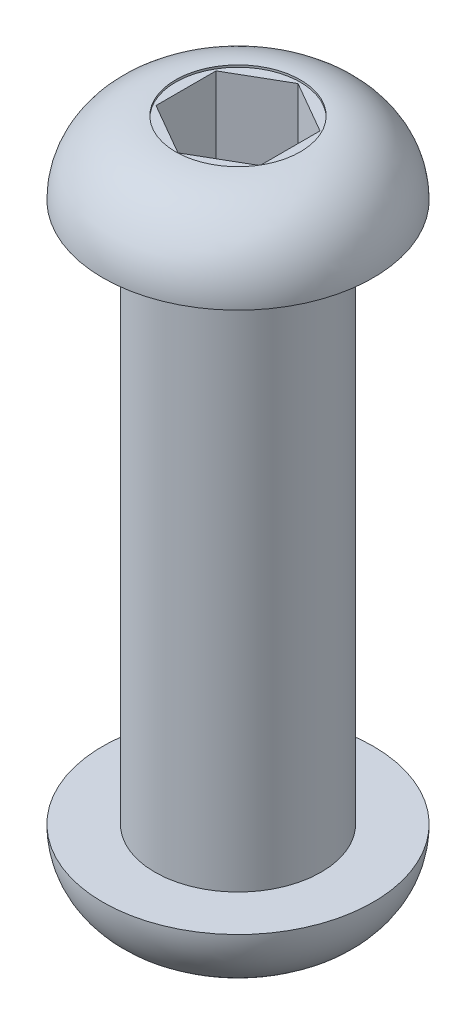
SolidWorks part; units mm, degrees
note: The reader was unsure of these and kept them because the rebuilt part matched: shared geometry of "Sketch1<4>".
ref_plane "Front Plane" through (0, 0, 0) normal (0, 0, 1) x (1, 0, 0)
ref_plane "Top Plane" through (0, 0, 0) normal (0, 1, 0) x (1, 0, 0)
ref_plane "Right Plane" through (0, 0, 0) normal (1, 0, 0) x (0, 0, -1)
sketch "Sketch1" plane through (0, 0, 0) normal (0, 1, 0) x (1, 0, 0)
  line L1 (0, 1.4434) -> (-1.25, 0.7217)
  line L2 (-1.25, 0.7217) -> (-1.25, -0.7217)
  line L3 (-1.25, -0.7217) -> (0, -1.4434)
  line L4 (0, -1.4434) -> (1.25, -0.7217)
  line L5 (1.25, -0.7217) -> (1.25, 0.7217)
  line L6 (1.25, 0.7217) -> (0, 1.4434)
  circle A0 centre (0, 0) radius 3.25
  circle A1 centre (0, 0) radius 1.25 construction
  circle A2 centre (0, 0) radius 2
  dimension "D1" = 6.5
  dimension "D2" = 4
extrude "Boss-Extrude1" add sketch "Sketch1" along normal blind 1.75 and the other way blind 14.75 contours A2 L6 L5 L4 L3 L2 L1 | A0 A2 | L5 L6 L1 L2 L3 L4
fillet "Fillet1" radius 1.75 1 edges at (0, 1.75, 3.25)
sketch "Sketch7" plane through (0, 1.75, 0) normal (0, 1, 0) x (1, 0, 0)
  circle A1 centre (0, 0) radius 1.5
  circle A2 centre (0, 0) radius 1.5
  dimension "D1" = 0
extrude "Cut-Extrude2" cut sketch "Sketch7" against normal blind 0.05
extrude "Cut-Extrude3" cut sketch "Sketch1<4>" against normal blind 13 contours A0 A2
sketch "Sketch1<4>" plane through (0, 0, 0) normal (0, 1, 0) x (1, 0, 0) same geometry as "Sketch1"
fillet "Fillet2" radius 1.75 1 edges at (0, -14.75, 3.25)
sketch "Sketch8" plane through (0, -14.75, 0) normal (0, -1, 0) x (1, 0, 0)
  circle A1 centre (0, 0) radius 1.5
  circle A2 centre (0, 0) radius 1.5
  dimension "D1" = 0
extrude "Cut-Extrude4" cut sketch "Sketch8" against normal blind 0.05
